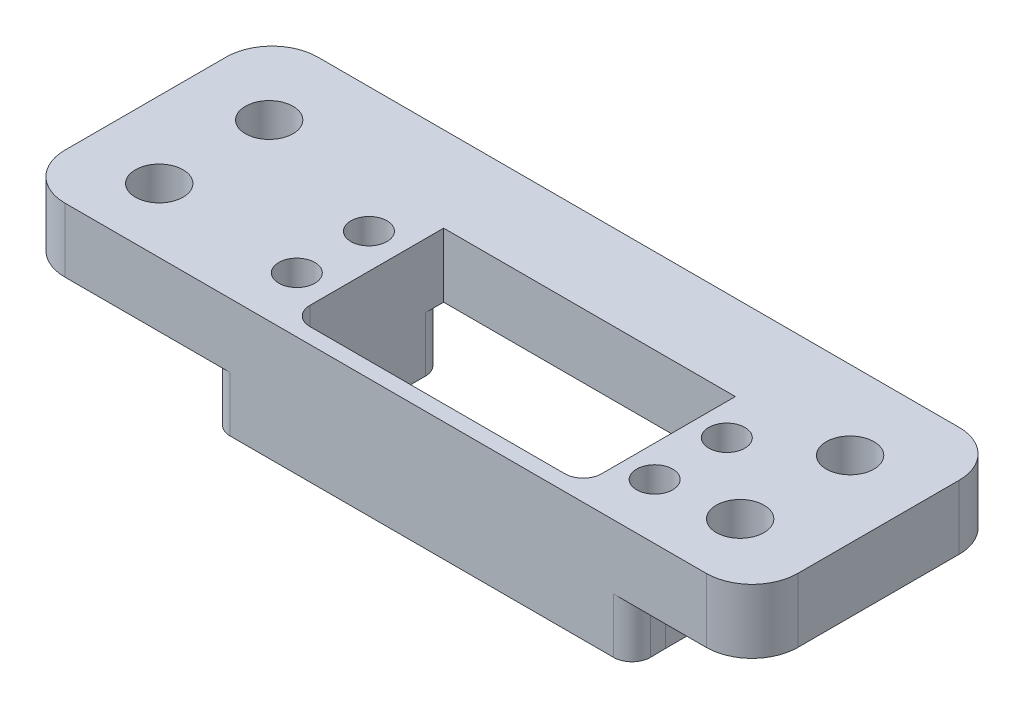
SolidWorks part; units mm, degrees
ref_plane "Front Plane" through (0, 0, 0) normal (0, 0, 1) x (1, 0, 0)
ref_plane "Top Plane" through (0, 0, 0) normal (0, 1, 0) x (1, 0, 0)
ref_plane "Right Plane" through (0, 0, 0) normal (1, 0, 0) x (0, 0, -1)
sketch "Sketch1" plane through (0, 0, 0) normal (0, 1, 0) x (1, 0, 0)
  line L1 (0, 0) -> (101.6, 0)
  line L2 (0, 0) -> (0, 35.052)
  line L3 (0, 35.052) -> (101.6, 35.052)
  line L4 (101.6, 0) -> (101.6, 35.052)
  dimension "1.38" = 35.052
  dimension "D2" = 101.6
extrude "Initial Extrude" add sketch "Sketch1" along normal blind 8.89 contours L2 L3 L4 L1
sketch "Sketch2" plane through (0, 8.89, 0) normal (0, 1, 0) x (1, 0, 0)
  line L0 (0, 0) -> (101.6, 0) construction
  line L1 (0, 0) -> (0, 35.052) construction
  line L2 (101.6, 0) -> (101.6, 35.052) construction
  circle A0 centre (10.541, 24.13) radius 3.302
  circle A1 centre (10.541, 8.89) radius 3.302
  circle A2 centre (91.059, 24.13) radius 3.302
  circle A3 centre (91.059, 8.89) radius 3.302
  dimension "D1" = 6.604
  dimension "D2" = 15.24
  dimension "D3" = 8.89
  dimension "D4" = 80.518
  dimension "D5" = 10.541
  dimension "D6" = 10.541
extrude "Screw Holes" cut sketch "Sketch2" against normal through all contours A1 | A2 | A0 | A3 region at (10.541, 8.89, -8.89) region at (91.059, 8.89, -24.13)
sketch "Sketch4" plane through (0, 8.89, 0) normal (0, 1, 0) x (1, 0, 0)
  line L0 (30.8, 17.7) -> (30.8, 7.7)
  line L1 (35.6087, 23.241) -> (76.041, 23.241)
  line L2 (35.6087, 23.241) -> (35.6087, 2.159)
  line L3 (35.6087, 2.159) -> (76.041, 2.159)
  line L4 (76.041, 23.241) -> (76.041, 2.159)
  line L5 (101.6, 0) -> (101.6, 35.052) construction
  line L7 (0, 0) -> (101.6, 0) construction
  circle A3 centre (65.5, 12.7) radius 10.541
  circle A4 centre (30.8, 17.7) radius 2.5
  circle A5 centre (30.8, 7.7) radius 2.5
  circle A6 centre (80.4, 17.7) radius 2.5
  circle A7 centre (80.4, 7.7) radius 2.5
  point P4 (35.6087, 12.7)
  point P20 (30.8, 12.7)
  dimension "D1" = 5
  dimension "D2" = 10
  dimension "D4" = 21.082
  dimension "D5" = 49.6
  dimension "D6" = 12.7
  dimension "D7" = 36.1
  dimension "D8" = 14.9
extrude "Servo Hole" cut sketch "Sketch4" against normal through all contours L4 L1 L2 L3 | A3 | A3 L4 L1 | A3 L3 L4 | A5 | A6 | A7 | A4 region at (32.5178, 8.89, -9.4178) region at (46.543, 8.89, -12.7) region at (73.6865, 8.89, -20.8865) region at (65.5, 8.89, -12.7) region at (73.6865, 8.89, -4.5135) region at (80.4, 8.89, -17.7) region at (80.4, 8.89, -7.7)
fillet "Fillet1" radius 6.35 4 edges at (101.6, 4.445, -35.052) (101.6, 4.445, 0) (0, 4.445, 0) (0, 4.445, -35.052)
sketch "Sketch6" plane through (0, 0, 0) normal (0, -1, 0) x (-1, 0, 0)
  circle A0 centre (-10.541, 8.89) radius 5.715
  circle A1 centre (-10.541, 24.13) radius 5.715
  circle A2 centre (-91.059, 24.13) radius 5.715
  circle A3 centre (-91.059, 8.89) radius 5.715
  circle A4 centre (-10.541, 24.13) radius 3.302 construction
  circle A6 centre (-91.059, 24.13) radius 3.302 construction
  circle A7 centre (-91.059, 8.89) radius 3.302 construction
  dimension "D1" = 11.43
extrude "Screw Head Hole" cut sketch "Sketch6" against normal blind 3.81
sketch "Sketch7" plane through (0, 0, 0) normal (0, -1, 0) x (1, 0, 0)
  line L0 (35.6087, -23.241) -> (76.041, -23.241) construction
  line L1 (35.6087, -2.159) -> (26.7187, -2.159)
  line L2 (35.6087, -2.159) -> (35.6087, -23.241)
  line L3 (35.6087, -23.241) -> (26.7187, -23.241)
  line L4 (26.7187, -2.159) -> (26.7187, -23.241)
  line L5 (76.041, -2.159) -> (84.931, -2.159)
  line L6 (76.041, -2.159) -> (76.041, -23.241)
  line L7 (76.041, -23.241) -> (84.931, -23.241)
  line L8 (84.931, -2.159) -> (84.931, -23.241)
  circle A20 centre (30.8, -7.7) radius 2.55
  circle A21 centre (30.8, -17.7) radius 2.55
  circle A22 centre (80.4, -7.7) radius 2.55
  circle A23 centre (80.4, -17.7) radius 2.55
  dimension "D1" = 8.89
  dimension "D2" = 8.89
extrude "Boss-Extrude1" add sketch "Sketch7" along normal blind 7.62
fillet "Fillet2" radius 2.54 8 edges at (35.6087, -3.81, -23.241) (76.041, -3.81, -23.241) (84.931, -3.81, -23.241) (26.7187, -3.81, -23.241) (76.041, -3.81, -2.159) (35.6087, -3.81, -2.159) (84.931, -3.81, -2.159) (26.7187, -3.81, -2.159)
sketch "Sketch8" plane through (0, 0, 0) normal (0, -1, 0) x (1, 0, 0)
  line L0 (26.7187, -4.699) -> (26.7187, 0)
  line L1 (6.35, 0) -> (95.25, 0) construction
  line L2 (26.7187, 0) -> (84.9973, 0)
  line L3 (84.9973, 0) -> (84.931, -4.699)
  line L4 (84.931, -20.701) -> (84.931, -4.699) construction
  line L5 (26.7187, -4.699) -> (35.6087, -4.699)
  line L6 (35.6087, -20.701) -> (35.6087, -4.699) construction
  line L7 (35.6087, -4.699) -> (35.6087, -2.159)
  line L8 (35.6087, -2.159) -> (76.041, -2.159)
  line L9 (76.041, -2.159) -> (76.041, -4.699)
  line L10 (76.041, -4.699) -> (84.931, -4.699)
extrude "Boss-Extrude2" add sketch "Sketch8" along normal up to surface (7.62 mm away) up to face at (31.1637, -7.62, -12.7)
fillet "Fillet3" radius 2.54 4 edges at (84.9973, -3.81, 0) (26.7187, -3.81, 0) (76.041, 0.635, -2.159) (35.6087, 0.635, -2.159)
